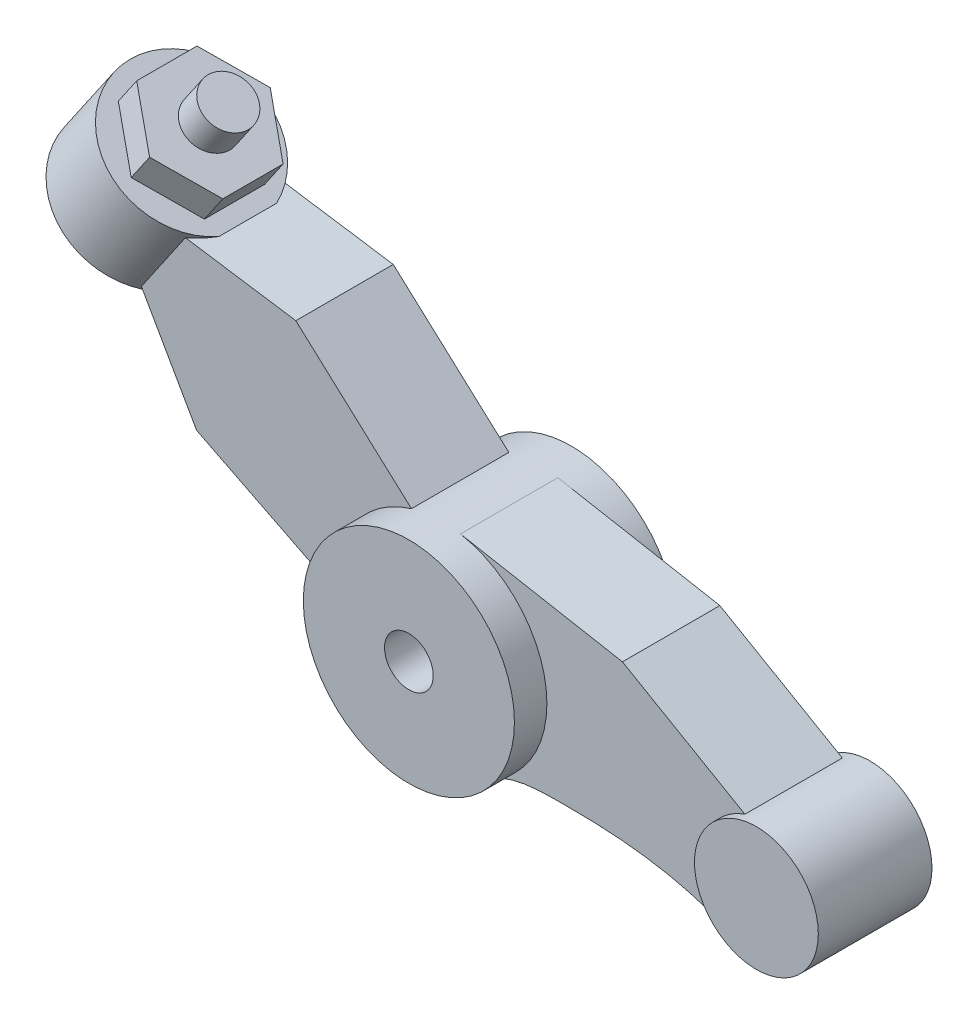
SolidWorks part; units mm, degrees
ref_plane "Front Plane" through (0, 0, 0) normal (0, 0, 1) x (1, 0, 0)
ref_plane "Top Plane" through (0, 0, 0) normal (0, 1, 0) x (1, 0, 0)
ref_plane "Right Plane" through (0, 0, 0) normal (1, 0, 0) x (0, 0, -1)
sketch "Sketch1" plane through (0, 0, 0) normal (0, 0, 1) x (1, 0, 0)
  line L0 (-3.3756, 0) -> (4.0945, 0) construction
  line L1 (0, 2.0641) -> (0, -2.2776) construction
  line L2 (0, 0) -> (-3.6604, 2.5129) construction
  line L3 (3.7376, 0.041) -> (3.7382, 0.0411)
  line L4 (3.7382, 0.0411) -> (2.2304, 0.9129)
  line L5 (2.2304, 0.9129) -> (0.2343, 1.2787)
  line L6 (-3.468, 2.7932) -> (-3.8529, 2.2326)
  line L7 (-3.468, 2.7932) -> (-1.7923, 2.5401)
  line L8 (-1.7923, 2.5401) -> (-0.3688, 1.2466)
  line L9 (-3.8529, 2.2326) -> (-3.0145, 0.7598)
  line L10 (-3.0145, 0.7598) -> (-1.2958, -0.1038)
  circle A0 centre (0, 0) radius 1.3
  circle A1 centre (0, 0) radius 0.3
  circle A2 centre (3.98, -0.682) radius 0.7625
  spline S0 degree 3 poles (3.5334, -1.3) (2.8536, -1.013) (1.9103, -0.9422) (0.8886, -0.9823) (0.6709, -1.1135) knots 0 0 0 0 0.740051 1 1 1 1
  point P25 (0, 0)
  dimension "D1" = 2.6
  dimension "D2" = 0.6
  dimension "D3" = 1.525
  dimension "D6" = 4.44
  dimension "D4" = 0.682
  dimension "D5" = 3.98
  dimension "D7" = 0.68
  dimension "D8" = 0.819
  dimension "D9" = 34.47
extrude "Boss-Extrude1" add sketch "Sketch1" along normal mid plane 2 contours A0 A1 region at (-0.5769, -1.1238, 0)
extrude "Boss-Extrude2" add sketch "Sketch1<3>" along normal mid plane 1.4 separate body contours A2
sketch "Sketch1<3>" plane through (0, 0, 0) normal (0, 0, 1) x (1, 0, 0) same geometry as "Sketch1"
extrude "Boss-Extrude3" add sketch "Sketch1<4>" along normal mid plane 1.2 contours S0 A2 L3 L4 L5 A0 region at (2.1701, -0.0682, 0)
sketch "Sketch1<4>" plane through (0, 0, 0) normal (0, 0, 1) x (1, 0, 0) same geometry as "Sketch1"
extrude "Boss-Extrude4" add sketch "Sketch1<6>" along normal mid plane 1.2 contours A0 L8 L7 L6 L9 L10 region at (-2.2002, 1.5105, 0)
sketch "Sketch1<6>" plane through (0, 0, 0) normal (0, 0, 1) x (1, 0, 0) same geometry as "Sketch1"
sketch "Sketch2" plane through (0, 0, 0) normal (0, 0, 1) x (1, 0, 0)
  line L0 (-3.8529, 2.2326) -> (-3.4454, 2.8262)
  line L1 (-3.4454, 2.8262) -> (-3.7751, 3.0526)
  line L2 (-3.7751, 3.0526) -> (-4.8378, 1.5047)
  line L3 (-4.3247, 1.9459) -> (-3.8529, 2.2326)
  line L4 (-3.468, 2.7932) -> (-3.8529, 2.2326) construction
  arc A0 (-4.8378, 1.5047) -> (-4.3247, 1.9459) centre (-4.6397, 1.7932) ccw
  point P8 (-4.3247, 1.9459)
  point P14 (-3.468, 2.7932)
  dimension "D3" = 0.35
  dimension "D1" = 0.72
  dimension "D2" = 0.4
  dimension "D4" = 1
revolve "Revolve1" add sketch "Sketch2" angle 360 about L2
sketch "Sketch3" plane through (0, 0, 0) normal (0, 0, 1) x (1, 0, 0)
  line L0 (-4.4294, 3.7127) -> (-3.6767, 3.196)
  line L1 (-3.6767, 3.196) -> (-4.2857, 2.3089)
  line L2 (-4.2857, 2.3089) -> (-5.0384, 2.8256)
  line L3 (-5.0384, 2.8256) -> (-4.4294, 3.7127)
  line L5 (-4.5124, 2.6854) -> (-3.8529, 2.2326) construction
  line L6 (-3.4454, 2.8262) -> (-4.1049, 3.279) construction
  point P2 (-4.1826, 2.459)
  point P5 (-3.7751, 3.0526)
  point P8 (0, 0)
  dimension "D1" = 1.076
  dimension "D2" = 0.913
revolve "Revolve2" add sketch "Sketch3" angle 360 about L1
sketch "Sketch4" plane through (0.3135, 0.4566, 0) normal (0.566, 0.8244, 0) x (0.8244, -0.566, 0)
  line L1 (-5.4833, -0.3714) -> (-4.84, -0.7428)
  line L2 (-4.84, -0.7428) -> (-4.1967, -0.3714)
  line L3 (-4.1967, -0.3714) -> (-4.1967, 0.3714)
  line L4 (-4.1967, 0.3714) -> (-4.84, 0.7428)
  line L5 (-4.84, 0.7428) -> (-5.4833, 0.3714)
  line L6 (-5.4833, 0.3714) -> (-5.4833, -0.3714)
  circle A0 centre (-4.84, 0) radius 0.6433 construction
  point P0 (-4.84, 0)
  dimension "D1" = 1.2866
extrude "Boss-Extrude6" add sketch "Sketch4" along normal blind 0.4
sketch "Sketch6" plane through (0.5399, 0.7864, 0) normal (0.566, 0.8244, 0) x (0.8244, -0.566, 0)
  circle A0 centre (-4.84, 0) radius 0.3
  dimension "D1" = 0.6
extrude "Boss-Extrude7" add sketch "Sketch6" along normal blind 0.4
